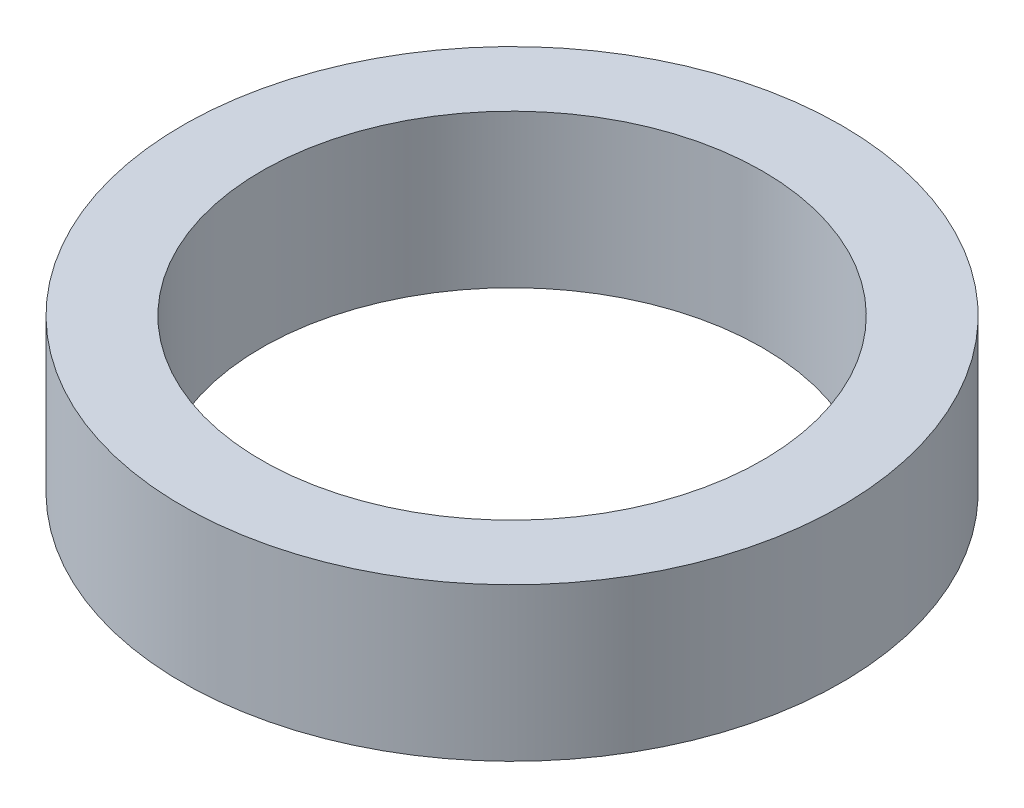
SolidWorks part; units mm, degrees
ref_plane "Front Plane" through (0, 0, 0) normal (0, 0, 1) x (1, 0, 0)
ref_plane "Top Plane" through (0, 0, 0) normal (0, 1, 0) x (1, 0, 0)
ref_plane "Right Plane" through (0, 0, 0) normal (1, 0, 0) x (0, 0, -1)
sketch "Sketch1" plane through (0, 0, 0) normal (0, 1, 0) x (1, 0, 0)
  circle A0 centre (0, 0) radius 62.5
  dimension "FLANGE_OD" = 125
extrude "Boss-Extrude1" add sketch "Sketch1" along normal blind 29
sketch "Sketch2" plane through (0, 0, 0) normal (0, 1, 0) x (1, 0, 0)
  circle A0 centre (0, 0) radius 47.5
  dimension "BORE_D" = 95
extrude "Cut-Extrude1" cut sketch "Sketch2" along normal through all
sketch "Sketch3" plane through (0, 29, 0) normal (0, 1, 0) x (1, 0, 0)
  circle A0 centre (0, 0) radius 29.3206 construction
  circle A1 centre (-29.3206, 0) radius 1.7031
  dimension "BOLT_D" = 3.4062
  dimension "BOLT_PCD" = 58.6413
extrude "Cut-Extrude2" cut sketch "Sketch3" against normal blind 24.0881 rebuild error yes
pattern_circular "CirPattern1" count 8 over 360 rebuild error yes
